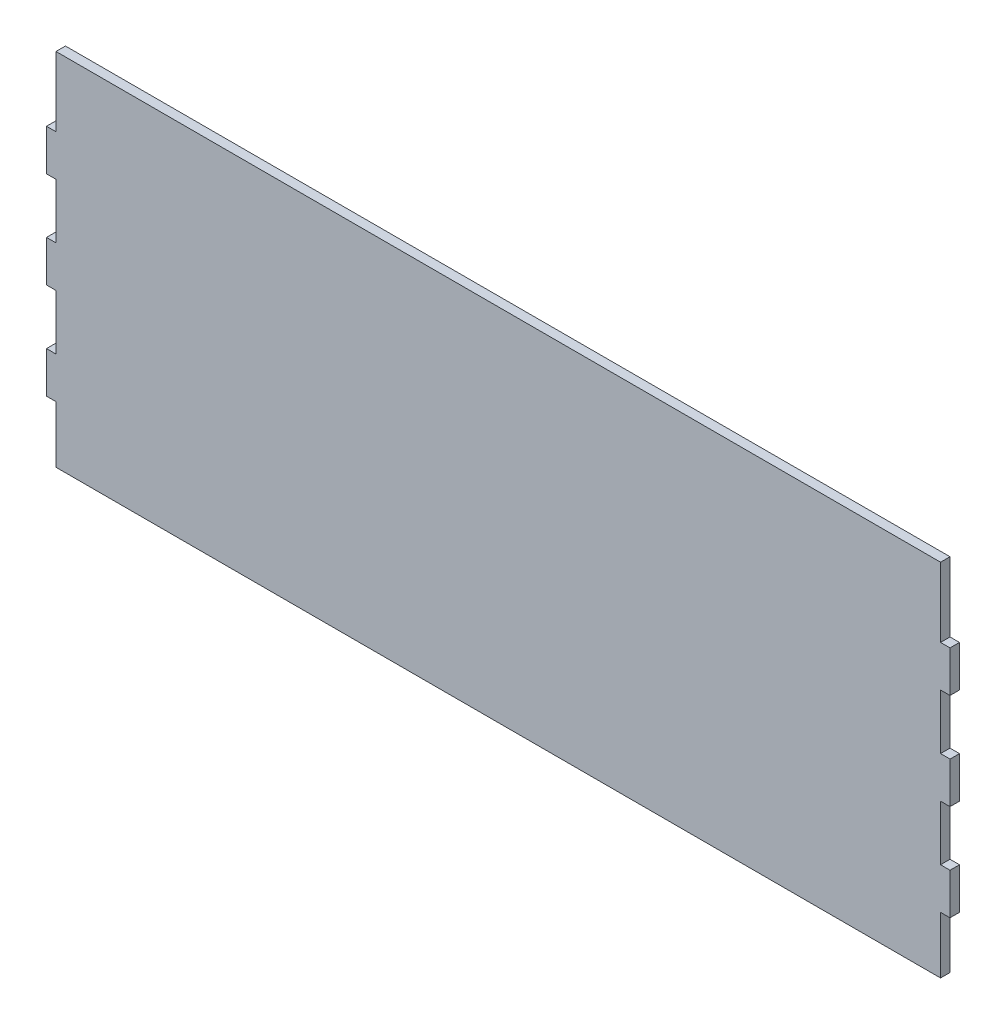
SolidWorks part; units mm, degrees
ref_plane "Front Plane" through (0, 0, 0) normal (0, 0, 1) x (1, 0, 0)
ref_plane "Top Plane" through (0, 0, 0) normal (0, 1, 0) x (1, 0, 0)
ref_plane "Right Plane" through (0, 0, 0) normal (1, 0, 0) x (0, 0, -1)
sketch "Croquis1" plane through (0, 0, 0) normal (0, 0, 1) x (1, 0, 0)
  line L1 (-143.015, 55) -> (143.015, 55)
  line L2 (-143.015, 55) -> (-143.015, -55)
  line L3 (-143.015, -55) -> (143.015, -55)
  line L4 (143.015, 55) -> (143.015, -55)
  line L5 (-143.015, 55) -> (143.015, -55) construction
  line L6 (-143.015, -55) -> (143.015, 55) construction
  point P0 (0, 0)
  dimension "D1" = 286.03
  dimension "D2" = 110
extrude "Saliente-Extruir1" add sketch "Croquis1" along normal blind 3
sketch "Croquis2" plane through (0, 0, 3) normal (0, 0, 1) x (1, 0, 0)
  line L0 (-143.015, 55) -> (-143.015, -55) construction
  line L1 (-143.015, 37) -> (-140.015, 37)
  line L2 (-143.015, 37) -> (-143.015, 23.9518)
  line L3 (-143.015, 23.9518) -> (-140.015, 23.9518)
  line L6 (-143.015, 6.5241) -> (-143.015, -6.5241)
  line L8 (-143.015, 6.5241) -> (-140.015, 6.5241)
  line L10 (-143.015, -6.5241) -> (-140.015, -6.5241)
  line L11 (-143.015, -23.9518) -> (-143.015, -37)
  line L12 (-143.015, -23.9518) -> (-140.015, -23.9518)
  line L14 (-143.015, -37) -> (-140.015, -37)
  line L15 (-143.015, -55) -> (143.015, -55) construction
  line L16 (143.015, 55) -> (-143.015, 55) construction
  line L17 (0, -55) -> (0, 55) construction
  line L18 (143.015, -23.9518) -> (140.015, -23.9518)
  line L19 (-140.015, -52) -> (140.015, -52)
  line L20 (140.015, -52) -> (140.015, 52)
  line L21 (-140.015, 52) -> (-140.015, -52)
  line L22 (140.015, 52) -> (-140.015, 52)
  line L24 (140.015, -52) -> (140.015, -37)
  line L25 (-140.015, 52) -> (-140.015, 37)
  line L28 (143.015, -37) -> (140.015, -37)
  line L29 (143.015, -23.9518) -> (143.015, -37)
  line L30 (143.015, 6.5241) -> (140.015, 6.5241)
  line L32 (143.015, -6.5241) -> (140.015, -6.5241)
  line L33 (143.015, 6.5241) -> (143.015, -6.5241)
  line L34 (143.015, 23.9518) -> (140.015, 23.9518)
  line L36 (143.015, 37) -> (140.015, 37)
  line L37 (143.015, 37) -> (143.015, 23.9518)
  line L38 (-140.015, 23.9518) -> (-140.015, 6.5241)
  line L39 (-140.015, -6.5241) -> (-140.015, -23.9518)
  line L40 (-140.015, -37) -> (-140.015, -52)
  line L41 (140.015, -23.9518) -> (140.015, -6.5241)
  line L42 (140.015, 6.5241) -> (140.015, 23.9518)
  line L43 (140.015, 37) -> (140.015, 52)
  line L44 (-140.015, 52) -> (-140.015, 55)
  line L45 (140.015, 52) -> (140.015, 55)
  line L46 (-140.015, -52) -> (-140.015, -55)
  line L47 (140.015, -52) -> (140.015, -55)
  line L48 (-140.015, -55) -> (140.015, -55)
  line L49 (-140.015, 55) -> (140.015, 55)
  line M3 (143.015, -55) -> (143.015, 55)
  line M4 (143.015, 55) -> (-143.015, 55)
  line M5 (-143.015, 55) -> (-143.015, -55)
  line M6 (-143.015, -55) -> (143.015, -55)
  dimension "D3" = 18
  dimension "D4" = 18
  dimension "D1" = 3
  dimension "D2" = 3
extrude "Cortar-Extruir1" cut sketch "Croquis2" against normal blind 3 contours L25 L44 L1 M4 M5 | L38 L3 L8 M5 | L45 L43 L36 M3 M4 | L42 L30 L34 M3 | L41 L18 L32 M3 | L24 L47 L28 M6 M3 | L39 L10 L12 M5 | L46 L40 L14 M5 M6 region at (-141.515, 46, 3) region at (-141.515, 15.238, 3) region at (141.515, 46, 3) region at (-141.515, -15.238, 3) region at (141.515, 15.238, 3) region at (-141.515, -46, 3) region at (141.515, -15.238, 3) region at (141.515, -46, 3)
sketch "Croquis4" plane through (0, 0, 0) normal (0, 0, -1) x (-1, 0, 0)
  line L6 (140.015, 55) -> (140.015, 37) construction
  line L7 (-140.015, 55) -> (140.015, 55)
  line L8 (-140.015, 55) -> (-140.015, 59)
  line L9 (-140.015, 59) -> (140.015, 59)
  line L10 (140.015, 55) -> (140.015, 59)
  dimension "D1" = 4
extrude "Saliente-Extruir3" add sketch "Croquis4" against normal blind 3
sketch "Croquis6" plane through (0, 0, 0) normal (0, 0, -1) x (-1, 0, 0)
  line L0 (-100.0921, -10.7078) -> (100.0921, -10.7078) construction
  text T0 "ITAM MANTIS" font "Century Gothic" height 25
  point P2 (0, -10.7078)
